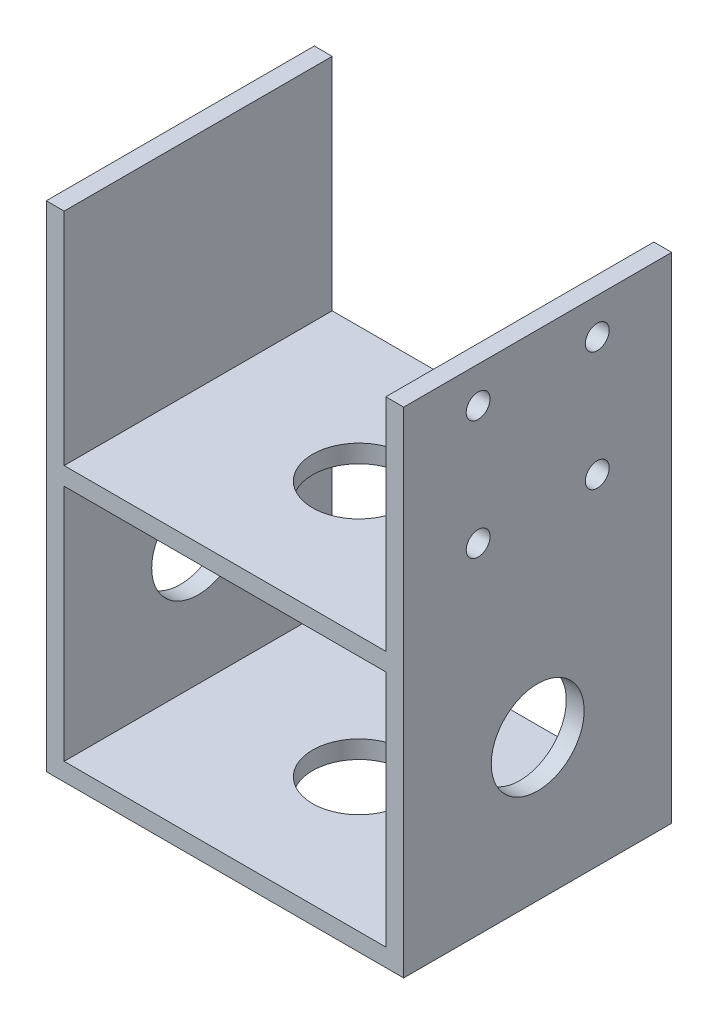
SolidWorks part; units mm, degrees
material "6061 Alloy"
ref_plane "Front Plane" through (0, 0, 0) normal (0, 0, 1) x (1, 0, 0)
ref_plane "Top Plane" through (0, 0, 0) normal (0, 1, 0) x (1, 0, 0)
ref_plane "Right Plane" through (0, 0, 0) normal (1, 0, 0) x (0, 0, -1)
sketch "Sketch1" plane through (0, 0, 0) normal (0, 1, 0) x (1, 0, 0)
  line L1 (30, -22.5) -> (-30, -22.5)
  line L2 (30, -22.5) -> (30, 22.5)
  line L3 (30, 22.5) -> (-30, 22.5)
  line L4 (-30, -22.5) -> (-30, 22.5)
  line L5 (30, -22.5) -> (-30, 22.5) construction
  line L6 (30, 22.5) -> (-30, -22.5) construction
  point P1 (0, 0)
  dimension "50" = 60
  dimension "D2" = 45
extrude "Boss-Extrude1" add sketch "Sketch1" along normal blind 3
sketch "Sketch5" plane through (0, 3, 0) normal (0, 1, 0) x (1, 0, 0)
  line L0 (-30, -22.5) -> (30, -22.5) construction
  line L1 (30, 22.5) -> (27, 22.5)
  line L2 (30, 22.5) -> (30, -22.5)
  line L3 (30, -22.5) -> (27, -22.5)
  line L4 (27, 22.5) -> (27, -22.5)
  line L7 (-30, 22.5) -> (-27, 22.5)
  line L8 (-30, 22.5) -> (-30, -22.5)
  line L9 (-30, -22.5) -> (-27, -22.5)
  line L10 (-27, 22.5) -> (-27, -22.5)
  dimension "D1" = 3
  dimension "D2" = 3
extrude "Boss-Extrude3" add sketch "Sketch5" along normal blind 35
sketch "Sketch9" plane through (0, 3, 0) normal (0, 1, 0) x (1, 0, 0)
  circle A0 centre (0, 0) radius 7.8
extrude "Cut-Extrude5" cut sketch "Sketch9" against normal blind 10
sketch "Sketch11" plane through (-30, 0, 0) normal (-1, 0, 0) x (0, 0, 1)
  line L0 (0, 0) -> (0, 38) construction
  line L5 (-22.5, 0) -> (22.5, 0) construction
  line L6 (-22.5, 38) -> (22.5, 38) construction
  line L7 (0, 38) -> (0, 19) construction
  line L8 (0, 19) -> (0, 28.5) construction
  line L9 (0, 28.5) -> (0, 19)
  circle A1 centre (0, 23.75) radius 7.8
extrude "Cut-Extrude8" cut sketch "Sketch11" against normal through all contours A1 region at (-30, 23.75, -7.5794)
sketch "Sketch12" plane through (0, 38, 0) normal (0, 1, 0) x (1, 0, 0)
  line L0 (-30, 22.5) -> (-27, 22.5)
  line L1 (-30, 22.5) -> (-30, -22.5)
  line L2 (-27, 22.5) -> (-27, -22.5)
  line L3 (-30, -22.5) -> (-27, -22.5)
  line L4 (27, 22.5) -> (30, 22.5)
  line L5 (27, 22.5) -> (27, -22.5)
  line L6 (30, 22.5) -> (30, -22.5)
  line L7 (27, -22.5) -> (30, -22.5)
  line L8 (27, -22.5) -> (30, -22.5) construction
  line L9 (-30, -22.5) -> (-27, -22.5) construction
extrude "Boss-Extrude4" add sketch "Sketch12" along normal blind 45
sketch "Sketch13" plane through (30, 0, 0) normal (1, 0, 0) x (0, 0, -1)
  line L0 (0, 83) -> (0, 31.55) construction
  line L1 (-22.5, 83) -> (22.5, 83) construction
  line L2 (0, 66.9557) -> (22.5, 66.9557) construction
  line L3 (22.5, 83) -> (22.5, 0) construction
  circle A0 centre (-10, 76.9557) radius 2
  circle A2 centre (0, 23.75) radius 7.8 construction
  circle A3 centre (10, 76.9557) radius 2
  circle A4 centre (10, 56.9557) radius 2
  circle A5 centre (-10, 56.9557) radius 2
  dimension "D3" = 4
  dimension "D1" = 10
  dimension "D2" = 10
extrude "Cut-Extrude9" cut sketch "Sketch13" against normal blind 10
ref_plane "Plane1" through (0, 23, 0) normal (0, 1, 0) x (1, 0, 0)
mirror "Mirror1" about plane through (0, 23, 0) normal (0, 1, 0) of "Cut-Extrude5", "Boss-Extrude1"
sketch "Sketch15" plane through (0, 83, 0) normal (0, 1, 0) x (1, 0, 0)
  line L0 (-30, 22.5) -> (30, 22.5)
  line L1 (-30, 22.5) -> (-30, -22.526)
  line L2 (30, 22.5) -> (30, -22.526)
  line L3 (-30, -22.526) -> (30, -22.526)
extrude "Boss-Extrude5" [suppressed] add sketch "Sketch15" along normal blind 3
sketch "Sketch16" [suppressed] plane through (0, 86, 0) normal (0, 1, 0) x (1, 0, 0)
  circle A0 centre (0, 0) radius 10.5
  circle A1 centre (0, 0) radius 13 construction
  circle A2 centre (0, 13) radius 1.5
  circle A3 centre (13, 0) radius 1.5
  circle A4 centre (0, -13) radius 1.5
  circle A5 centre (-13, 0) radius 1.5
  point P15 (0, 0)
  dimension "D1" = 21
  dimension "D2" = 3
  dimension "D4" = 26
  dimension "D3" = 4
extrude "Cut-Extrude10" [suppressed] cut sketch "Sketch16" against normal blind 3
